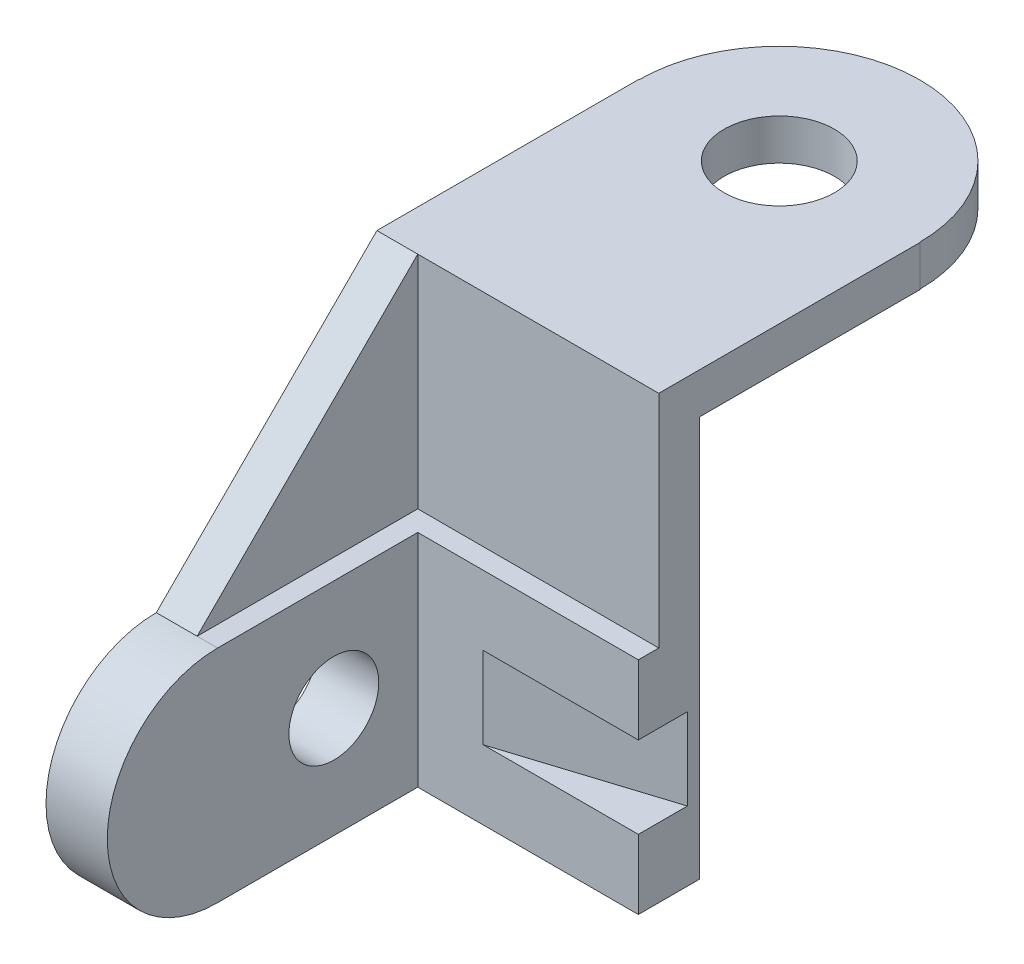
SolidWorks part; units mm, degrees
ref_plane "Front Plane" through (0, 0, 0) normal (0, 0, 1) x (1, 0, 0)
ref_plane "Top Plane" through (0, 0, 0) normal (0, 1, 0) x (1, 0, 0)
ref_plane "Right Plane" through (0, 0, 0) normal (1, 0, 0) x (0, 0, -1)
sketch "Sketch2" plane through (0, 0, 0) normal (1, 0, 0) x (0, 0, -1)
  line L0 (0, 0) -> (0, 54)
  line L1 (0, 54) -> (-54, 0)
  line L2 (-54, 0) -> (0, 0)
  line L3 (-75.4406, -27) -> (24.3504, -27) construction
  line L4 (0, 0) -> (-54, 0)
  line L5 (0, 0) -> (0, -54)
  line L6 (0, -54) -> (-54, -54)
  line L7 (-54, 0) -> (-54, -54)
  line L8 (-27, -71.1876) -> (-27, 28.8599) construction
  circle A0 centre (-25.5451, -27) radius 11
  arc A1 (-54, 0) -> (-54, -54) centre (-54, -27) ccw
  dimension "D1" = 54
  dimension "D2" = 54
  dimension "D3" = 54
  dimension "D4" = 27
  dimension "D5" = 27
extrude "Boss-Extrude1" add sketch "Sketch2" along normal blind 10 contours L1 L2 L0 region at (0, 18, 18)
extrude "Boss-Extrude2" add sketch "Sketch2<3>" along normal blind 15 contours L2 L7 L6 L5 A0 | L7 A1 region at (0, -27, 0.7637) region at (0, -27, 65.4592)
sketch "Sketch2<3>" plane through (0, 0, 0) normal (1, 0, 0) x (0, 0, -1) same geometry as "Sketch2"
sketch "Sketch3" plane through (0, 0, 0) normal (0, 0, -1) x (-1, 0, 0)
  line L1 (0, 54) -> (-15, 54)
  line L2 (0, 54) -> (0, -54)
  line L3 (0, -54) -> (-15, -54)
  line L4 (-15, 54) -> (-15, -54)
extrude "Boss-Extrude3" add sketch "Sketch3" along normal blind 10
sketch "Sketch4" plane through (15, 0, 0) normal (1, 0, 0) x (0, 0, -1)
  line L0 (0, 54) -> (0, -54)
  line L2 (10, -54) -> (-54, -54) construction
  line L8 (0, 0) -> (-54, 0)
  line L9 (-54, -54) -> (10, -54)
  line L10 (10, -54) -> (10, 54)
  line L11 (10, 54) -> (0, 54)
  line L12 (0, 54) -> (0, 0)
  line L13 (0, 0) -> (-54, 0)
  line L14 (-54, -54) -> (0, -54)
  line L17 (0, 54) -> (0, 0)
  arc A1 (-54, 0) -> (-54, -54) centre (-54, -27) ccw
  arc A2 (-54, 0) -> (-54, -54) centre (-54, -27) ccw
  line M11 (-54, -54) -> (10, -54)
  line M12 (10, -54) -> (10, 54)
  line M13 (10, 54) -> (0, 54)
  line M14 (0, 54) -> (0, 0)
  dimension "D1" = 0
extrude "Boss-Extrude4" add sketch "Sketch4" along normal blind 54 contours L0 M14 M11 M12 M13 region at (15, 0, -5)
sketch "Sketch5" plane through (0, 0, 0) normal (0, 0, 1) x (1, 0, 0)
  line L0 (69, -54) -> (15, -54) construction
  line L1 (15, 0) -> (69, 0)
  line L2 (15, 0) -> (15, -54)
  line L3 (15, -54) -> (69, -54)
  line L4 (69, 0) -> (69, -54)
  line L5 (69, 54) -> (69, -54) construction
extrude "Boss-Extrude5" add sketch "Sketch5" along normal blind 5
sketch "Sketch8" plane through (0, 0, -10) normal (0, 0, -1) x (-1, 0, 0)
  line L0 (0, -54) -> (0, 54) construction
  line L1 (-69, 54) -> (0, 54)
  line L2 (-69, 54) -> (-69, 44)
  line L3 (-69, 44) -> (0, 44)
  line L4 (0, 54) -> (0, 44)
  dimension "D1" = 69
  dimension "D2" = 10
extrude "Boss-Extrude6" add sketch "Sketch8" along normal blind 54
sketch "Sketch10" plane through (0, 54, 0) normal (0, 1, 0) x (1, 0, 0)
  line L0 (0, 64) -> (69, 64) construction
  circle A0 centre (34.5, 64) radius 34.3951
  circle A1 centre (34.5, 64) radius 13.5
  dimension "D1" = 27
extrude "Boss-Extrude7" add sketch "Sketch10" against normal blind 10
sketch "Sketch11" plane through (0, 54, 0) normal (0, 1, 0) x (1, 0, 0)
  line L0 (21, 64) -> (48, 64) construction
  circle A0 centre (34.5, 64) radius 13.5
extrude "Cut-Extrude1" cut sketch "Sketch11" against normal blind 10
sketch "Sketch12" plane through (0, 0, 5) normal (0, 0, 1) x (1, 0, 0)
  line L0 (69, -54) -> (69, 0) construction
  line L1 (31, -17) -> (69, -17)
  line L2 (31, -17) -> (31, -37)
  line L3 (31, -37) -> (69, -37)
  line L4 (69, -17) -> (69, -37)
  line L5 (69, 0) -> (10, 0) construction
  dimension "D1" = 38
  dimension "D2" = 20
  dimension "D3" = 17
extrude "Cut-Extrude2" cut sketch "Sketch12" against normal blind 12
sketch "Sketch14" plane through (0, -37, 0) normal (0, 1, 0) x (1, 0, 0)
  line L0 (31, -5) -> (69, 7)
  line L1 (69, 7) -> (31, 7)
  line L2 (31, 7) -> (31, -5)
extrude "Boss-Extrude9" add sketch "Sketch14" along normal blind 20
